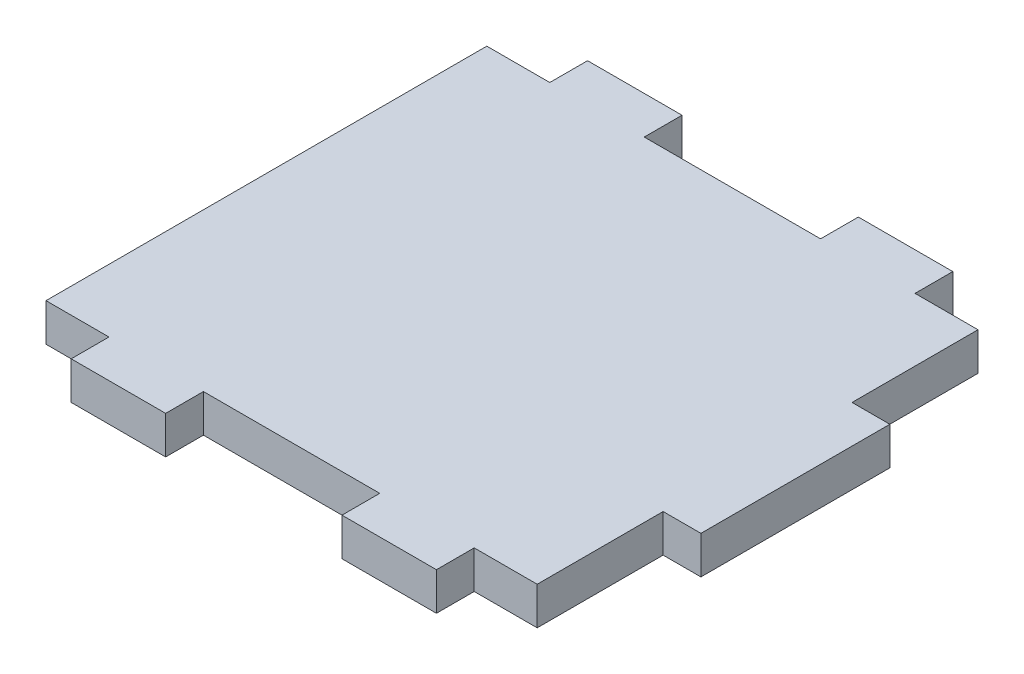
SolidWorks part; units mm, degrees
material "Acrylic (Medium-high impact)"
ref_plane "Front Plane" through (0, 0, 0) normal (0, 0, 1) x (1, 0, 0)
ref_plane "Top Plane" through (0, 0, 0) normal (0, 1, 0) x (1, 0, 0)
ref_plane "Right Plane" through (0, 0, 0) normal (1, 0, 0) x (0, 0, -1)
sketch "Sketch1" plane through (0, 0, 0) normal (0, 1, 0) x (1, 0, 0)
  line L10 (-179.9438, 52.5) -> (-169.9438, 52.5)
  line L11 (-179.9438, 52.5) -> (-179.9438, -17.5)
  line L12 (-179.9438, -17.5) -> (-169.9438, -17.5)
  line L13 (-101.9438, 52.5) -> (-101.9438, 32.5)
  line L14 (-101.9438, -17.5) -> (-101.9438, 52.5) construction
  line L15 (-179.9438, 58.5) -> (-179.9438, 52.5) construction
  line L17 (-169.9438, 52.5) -> (-169.9438, 58.5)
  line L18 (-169.9438, 58.5) -> (-154.9438, 58.5)
  line L19 (-154.9438, 52.5) -> (-154.9438, 58.5)
  line L21 (-126.9438, 52.5) -> (-126.9438, 58.5)
  line L22 (-126.9438, 58.5) -> (-111.9438, 58.5)
  line L23 (-111.9438, 52.5) -> (-111.9438, 58.5)
  line L26 (-169.9438, -17.5) -> (-169.9438, -23.5)
  line L27 (-169.9438, -23.5) -> (-154.9438, -23.5)
  line L28 (-154.9438, -17.5) -> (-154.9438, -23.5)
  line L30 (-126.9438, -17.5) -> (-126.9438, -23.5)
  line L31 (-126.9438, -23.5) -> (-111.9438, -23.5)
  line L32 (-111.9438, -17.5) -> (-111.9438, -23.5)
  line L33 (-101.9438, 32.5) -> (-95.9438, 32.5)
  line L35 (-101.9438, 2.5) -> (-95.9438, 2.5)
  line L36 (-95.9438, 32.5) -> (-95.9438, 2.5)
  line L37 (-154.9438, 52.5) -> (-126.9438, 52.5)
  line L38 (-111.9438, 52.5) -> (-101.9438, 52.5)
  line L39 (-101.9438, 2.5) -> (-101.9438, -17.5)
  line L40 (-111.9438, -17.5) -> (-101.9438, -17.5)
  line L41 (-154.9438, -17.5) -> (-126.9438, -17.5)
  dimension "D1" = 0
  dimension "D2" = 6
  dimension "D3" = 15
  dimension "D4" = 15
  dimension "D5" = 10
  dimension "D6" = 10
  dimension "D7" = 6
  dimension "D8" = 6
  dimension "D9" = 30
  dimension "D10" = 70
  dimension "D11" = 20
extrude "Boss-Extrude1" add sketch "Sketch1" along normal blind 6
